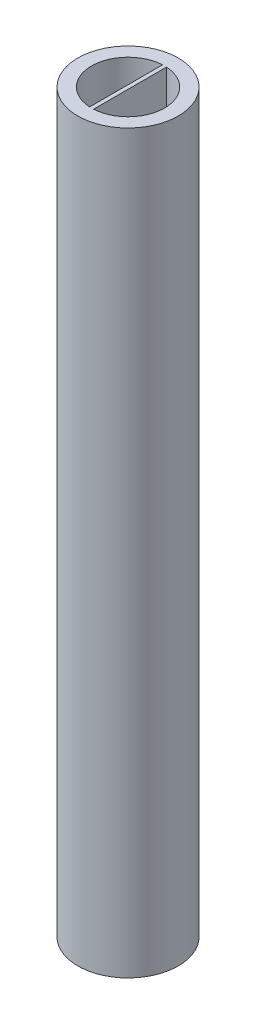
SolidWorks part; units mm, degrees
ref_plane "Front Plane" through (0, 0, 0) normal (0, 0, 1) x (1, 0, 0)
ref_plane "Top Plane" through (0, 0, 0) normal (0, 1, 0) x (1, 0, 0)
ref_plane "Right Plane" through (0, 0, 0) normal (1, 0, 0) x (0, 0, -1)
sketch "Sketch1" plane through (0, 0, 0) normal (0, 1, 0) x (1, 0, 0)
  line L0 (-0.1369, 2.5764) -> (-0.1369, -2.5764)
  line L1 (0.1395, 2.5762) -> (0.1395, -2.5762)
  arc A0 (-0.1369, 2.5764) -> (-0.1369, -2.5764) centre (0, 0) ccw
  circle A1 centre (0, 0) radius 3.55
  arc A2 (0.1395, -2.5762) -> (0.1395, 2.5762) centre (0, 0) ccw
  dimension "D1" = 5.16
extrude "Boss-Extrude1" add sketch "Sketch1" along normal blind 52
